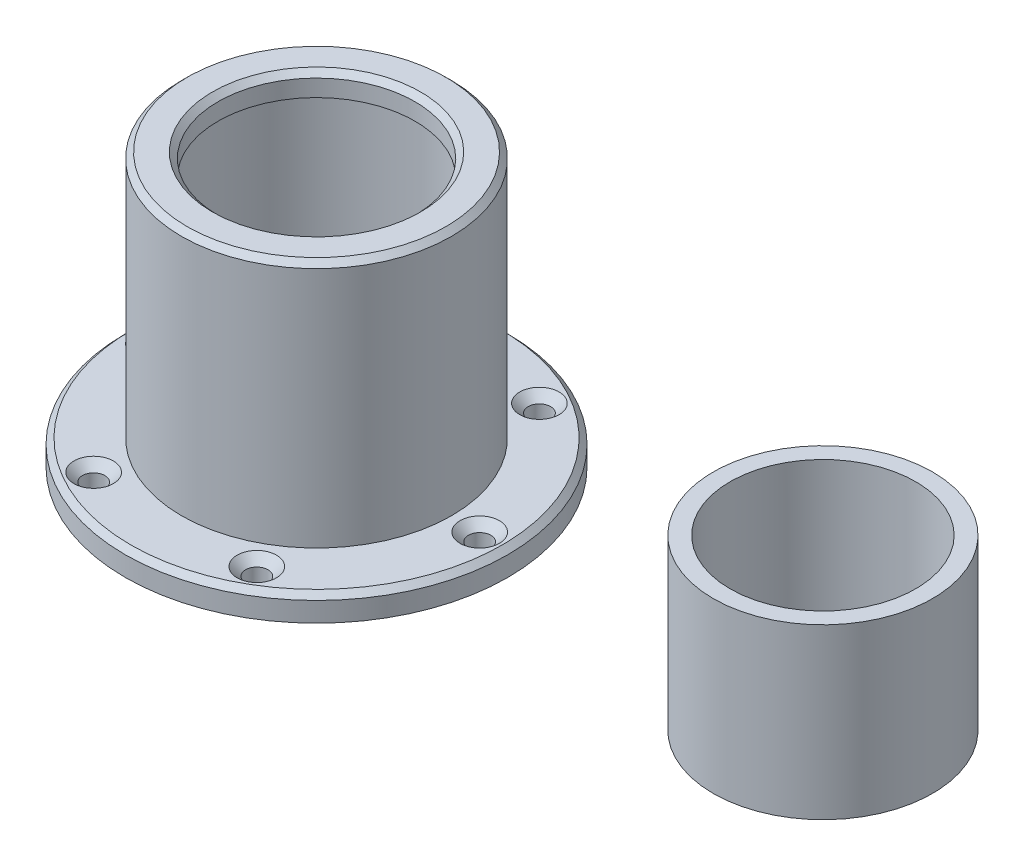
SolidWorks part; units mm, degrees
note: The reader was unsure of these and kept them because the rebuilt part matched: shared geometry of "Sketch1<3>", "Sketch1<4>", "Sketch4<3>".
ref_plane "Front Plane" through (0, 0, 0) normal (0, 0, 1) x (1, 0, 0)
ref_plane "Top Plane" through (0, 0, 0) normal (0, 1, 0) x (1, 0, 0)
ref_plane "Right Plane" through (0, 0, 0) normal (1, 0, 0) x (0, 0, -1)
sketch "Sketch1" plane through (0, 0, 0) normal (0, 1, 0) x (1, 0, 0)
  line L0 (34, 0) -> (24, 0) construction
  circle A0 centre (0, 0) radius 20
  circle A1 centre (0, 0) radius 24
  circle A2 centre (0, 0) radius 34
  circle A3 centre (29, 0) radius 2
  dimension "D1" = 40
  dimension "D2" = 4
  dimension "D3" = 4
  dimension "D4" = 10
extrude "Boss-Extrude1" add sketch "Sketch1" against normal blind 4.5
extrude "Boss-Extrude2" add sketch "Sketch1<3>" along normal blind 40 contours A1 A0
sketch "Sketch1<3>" plane through (0, 0, 0) normal (0, 1, 0) x (1, 0, 0) same geometry as "Sketch1"
sketch "Sketch2" plane through (0, 40, 0) normal (0, 1, 0) x (1, 0, 0)
  circle A0 centre (0, 0) radius 24
  circle A1 centre (0, 0) radius 17.5
  circle A3 centre (0, 0) radius 24 construction
  circle M2 centre (0, 0) radius 20
  circle M3 centre (0, 0) radius 24
  dimension "D1" = 35
extrude "Boss-Extrude3" add sketch "Sketch2" along normal blind 4 contours A1 M2 | M3 M2 | A1
chamfer "Chamfer1" distance 1 angle 45 3 edges at (0, 0, 34) (0, 44, 17.5) (0, 44, 24)
extrude "Cut-Extrude1" cut sketch "Sketch1<4>" against normal through all contours L0 A3 | A3 L0
sketch "Sketch1<4>" plane through (0, 0, 0) normal (0, 1, 0) x (1, 0, 0) same geometry as "Sketch1"
sketch "Sketch3" plane through (0, 0, 0) normal (0, 0, 1) x (1, 0, 0)
  line L0 (0, 0) -> (0, 44)
  line L1 (18.5, 44) -> (-18.5, 44) construction
chamfer "Chamfer2" distance 1.5 angle 45 1 edges at (29, 0, 2)
pattern_circular "CirPattern1" count 6 over 360 about axis through (0, 0, 0) along (0, 1, 0) of "Cut-Extrude1", "Chamfer2"
sketch "Sketch4" plane through (0, 0, 0) normal (0, 1, 0) x (1, 0, 0)
  line L0 (0, 0) -> (90, 0) construction
  line L3 (88.5, 25) -> (91.5, 25)
  line L4 (88.5, 25) -> (88.5, -25)
  line L5 (88.5, -25) -> (91.5, -25)
  line L6 (91.5, 25) -> (91.5, -25)
  line L7 (88.5, 25) -> (91.5, -25) construction
  line L8 (88.5, -25) -> (91.5, 25) construction
  line L9 (65, 1.5) -> (115, 1.5)
  line L10 (65, 1.5) -> (65, -1.5)
  line L11 (65, -1.5) -> (115, -1.5)
  line L12 (115, 1.5) -> (115, -1.5)
  line L13 (65, 1.5) -> (115, -1.5) construction
  line L14 (65, -1.5) -> (115, 1.5) construction
  circle A0 centre (90, 0) radius 19.5
  circle A1 centre (90, 0) radius 16.5
  circle A2 centre (90, 0) radius 20
  circle A5 centre (90, 0) radius 40
  circle A6 centre (0, 0) radius 20 construction
  dimension "D1" = 0.5
  dimension "D2" = 3
  dimension "D4" = 80
  dimension "D3" = 50
  dimension "D5" = 90
  dimension "D6" = 3
extrude "Boss-Extrude4" add sketch "Sketch4" along normal blind 3 separate body contours L9 A1 L11 L4 | A1 L9 A0 L11 | A2 L9 L10 L11 | L9 A2 L11 A0 | L4 L11 L6 L9 | L11 A1 L9 L6 | A1 L11 A0 L9 | L11 A2 L9 A0 | A2 L11 L12 L9
extrude "Boss-Extrude5" add sketch "Sketch4<3>" along normal blind 3 contours A2 L4 L5 L6 | A1 L4 A0 L6 | L4 A2 L6 A0 | L4 A1 L6 L11 | L6 A1 L4 L9 | A1 L6 A0 L4 | A2 L6 L3 L4 | L6 A2 L4 A0 | L4 L11 L6 L9
sketch "Sketch4<3>" plane through (0, 0, 0) normal (0, 1, 0) x (1, 0, 0) same geometry as "Sketch4"
pattern_linear "LPattern1" count 5 spacing 6 along (1, 0, 0) of "Boss-Extrude5"
pattern_linear "LPattern2" count 5 spacing 6 along (-1, 0, 0) of "Boss-Extrude5"
pattern_linear "LPattern3" count 5 spacing 6 along (0, 0, 1) of "Boss-Extrude4"
pattern_linear "LPattern4" count 5 spacing 6 along (0, 0, -1) of "Boss-Extrude4"
sketch "Sketch5" plane through (0, 0, 0) normal (0, 1, 0) x (1, 0, 0)
  circle A0 centre (90, 0) radius 40
  circle A1 centre (90, 0) radius 19.5
  circle A2 centre (90, 0) radius 19.5 construction
  circle A3 centre (90, 0) radius 40 construction
extrude "Cut-Extrude5" cut sketch "Sketch5" along normal through all contours A0 A1
sketch "Sketch6" plane through (0, 0, 0) normal (0, 1, 0) x (1, 0, 0)
  line L0 (88.5, -25) -> (91.5, 25) construction
  circle A0 centre (90, 0) radius 16.5
  circle A1 centre (90, 0) radius 19.5
  circle A2 centre (90, 0) radius 16.5 construction
  circle A3 centre (90, 0) radius 19.5 construction
extrude "Boss-Extrude7" add sketch "Sketch6" along normal blind 30
